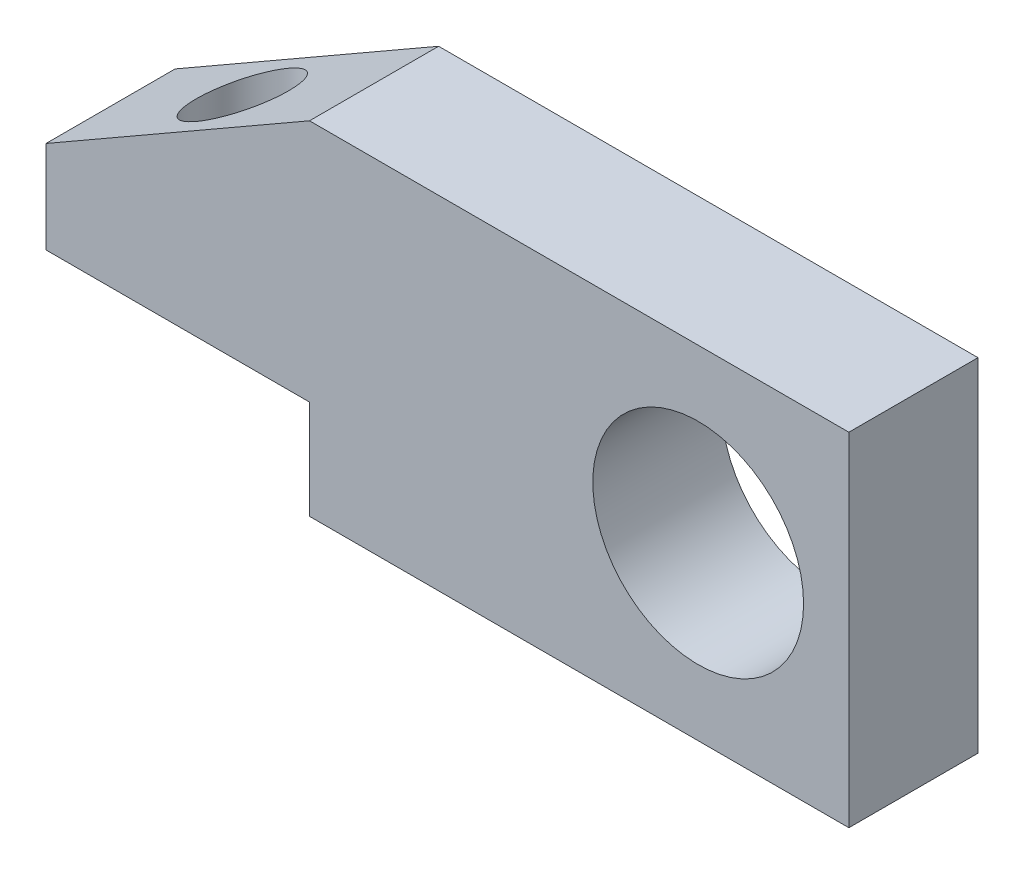
SolidWorks part; units mm, degrees
material "ABS"
ref_plane "Front Plane" through (0, 0, 0) normal (0, 0, 1) x (1, 0, 0)
ref_plane "Top Plane" through (0, 0, 0) normal (0, 1, 0) x (1, 0, 0)
ref_plane "Right Plane" through (0, 0, 0) normal (1, 0, 0) x (0, 0, -1)
sketch "Sketch1" plane through (0, 0, 0) normal (0, 0, 1) x (1, 0, 0)
  line L0 (-24, 15) -> (0, 15)
  line L1 (0, 15) -> (0, 0)
  line L2 (0, 0) -> (93, 0)
  line L3 (93, 0) -> (93, 102.7)
  line L4 (93, 102.7) -> (0, 102.7)
  line L5 (0, 102.7) -> (0, 30)
  line L6 (0, 30) -> (-24, 30)
  line L7 (-24, 30) -> (-24, 15)
  circle A0 centre (15, 10.5) radius 8
  circle A1 centre (70, 72) radius 11
  circle A2 centre (15, 10.5) radius 11
  dimension "D1" = 15
  dimension "D10" = 16
  dimension "D11" = 22
  dimension "D12" = 22
  dimension "D2" = 24
  dimension "D3" = 72.7
  dimension "D4" = 15
  dimension "D5" = 15
  dimension "D6" = 10.5
  dimension "D7" = 82.5061
  dimension "D8" = 72
  dimension "D9" = 93
extrude "Boss-Extrude1" add sketch "Sketch1" along normal blind 4.8 contours A2 L2 L3 L4 L5 L6 L7 L0 L1 A1 | L2 A2 A0 region at (44.5238, 51.0418, 0) region at (8.6656, 19.1141, 0)
sketch "Sketch2" plane through (0, 0, 4.8) normal (0, 0, 1) x (1, 0, 0)
  line L0 (93, 0) -> (93, 102.7) construction
  line L1 (48.1786, 92.7632) -> (93, 92.7632)
  line L2 (48.1786, 92.7632) -> (48.1786, 52.666)
  line L3 (48.1786, 52.666) -> (93, 52.666)
  line L4 (93, 92.7632) -> (93, 52.666)
  line L5 (48.1786, 92.7632) -> (93, 52.666) construction
  line L6 (48.1786, 52.666) -> (93, 92.7632) construction
  circle A0 centre (70, 72) radius 11
  circle A1 centre (70, 72) radius 4.15
  point P8 (70.5893, 72.7146)
  line M4 (93, 0) -> (93, 102.7)
  circle M10 centre (70, 72) radius 11
  dimension "D1" = 22
  dimension "D2" = 8.3
extrude "Boss-Extrude2" add sketch "Sketch2" along normal blind 8.2 contours L2 L3 L1 M4 M10 region at (70.5893, 92.1618, 4.8)
sketch "Sketch3" plane through (0, 0, 4.8) normal (0, 0, 1) x (1, 0, 0)
  line L1 (-24, 15) -> (0, 15)
  line L2 (-24, 15) -> (-24, 30)
  line L3 (-24, 30) -> (0, 30)
  line L4 (0, 15) -> (0, 30)
  line L5 (-24, 15) -> (0, 30) construction
  line L6 (-24, 30) -> (0, 15) construction
  line L7 (0, 0) -> (93, 0)
  line L8 (0, 0) -> (0, 52.666)
  line L9 (0, 52.666) -> (93, 52.666)
  line L10 (93, 0) -> (93, 52.666)
  circle A0 centre (15, 10.5) radius 8
  point P4 (-12, 22.5)
  point P11 (46.5, 26.333)
  circle M1 centre (15, 10.5) radius 8
  line M6 (0, 102.7) -> (0, 30)
  line M7 (0, 30) -> (-24, 30)
  line M8 (-24, 30) -> (-24, 15)
  line M9 (-24, 15) -> (0, 15)
  line M10 (0, 15) -> (0, 0)
  line M11 (0, 0) -> (93, 0)
  line M12 (93, 0) -> (93, 52.666)
  line M13 (93, 52.666) -> (48.1786, 52.666)
  dimension "D1" = 93
extrude "Boss-Extrude3" add sketch "Sketch3" along normal blind 5 contours L4 M9 M7 M8 | L9 L4 M6 M10 M11 M12 M13 M1 region at (-12, 22.5, 4.8) region at (47.8484, 27.0108, 4.8)
sketch "Sketch4" plane through (0, 83.2317, 0) normal (0, -1, 0) x (1, 0, 0)
  line L0 (0, 9.8) -> (0, 4.8) construction
  line L1 (0, 4.8) -> (48.1786, 4.8)
  line L2 (0, 4.8) -> (0, 45.3)
  line L3 (0, 45.3) -> (48.1786, 45.3)
  line L4 (48.1786, 4.8) -> (48.1786, 45.3)
  line L5 (0, 4.8) -> (48.1786, 45.3) construction
  line L6 (0, 45.3) -> (48.1786, 4.8) construction
  line L7 (0, 4.8) -> (48.1786, 4.8) construction
  line L8 (48.1786, 13) -> (48.1786, 9.8) construction
  line L9 (0, 0) -> (93, 0) construction
  line L10 (0, 45.3) -> (-5, 45.3)
  line L11 (0, 45.3) -> (0, 0)
  line L12 (0, 0) -> (-5, 0)
  line L13 (-5, 45.3) -> (-5, 0)
  line L14 (0, 45.3) -> (-5, 0) construction
  line L15 (0, 0) -> (-5, 45.3) construction
  circle A0 centre (13.9465, 30.3) radius 6.35
  circle A1 centre (13.9465, 23.3) radius 18.5
  circle A3 centre (29.4465, 23.3) radius 2
  circle A4 centre (21.6965, 9.8766) radius 2
  circle A5 centre (6.1965, 9.8766) radius 2
  point P10 (24.0893, 25.05)
  point P30 (-2.5, 22.65)
  arc M5 (5.039, 30.9329) -> (22.854, 30.9329) centre (13.9465, 30.3) ccw
  arc M7 (23.1854, 31.0672) -> (4.7077, 31.0672) centre (13.9465, 23.3) cw
  circle M9 centre (21.6965, 9.8766) radius 1.6
  circle M10 centre (6.1965, 9.8766) radius 1.6
  circle M11 centre (-1.5535, 23.3) radius 1.6
  circle M12 centre (6.1965, 36.7234) radius 1.6
  circle M13 centre (21.6965, 36.7234) radius 1.6
  circle M15 centre (27.3699, 31.05) radius 2.1
  circle M16 centre (0.5231, 31.05) radius 2.1
  circle M17 centre (13.9465, 7.8) radius 2.1
  circle M19 centre (13.9465, 23.3) radius 18.5
  dimension "D1" = 12.7
  dimension "D2" = 15
  dimension "D3" = 4
  dimension "D4" = 4
  dimension "D5" = 4
  dimension "D6" = 5
  dimension "D7" = 0
extrude "Boss-Extrude4" add sketch "Sketch4" along normal blind 5 contours L1 L4 L3 M19 | A0 L3 L2 A5 A4 A3 M12 M19 M16 M11 M13 M17 M15 M5 M7 | M5 M7 | M17 | A4 M9 | M9 | M10 | A5 M10 | M15 | L2 M16 | L2 L1 M19 region at (3.3557, 83.2317, 6.6306) region at (34.3643, 83.2317, 27.4815) region at (15.1399, 83.2317, 22.3686) region at (1.1393, 83.2317, 31.05) region at (19.7531, 83.2317, 9.8766) region at (4.2531, 83.2317, 9.8766) region at (21.6965, 83.2317, 9.8766) region at (6.1965, 83.2317, 9.8766) region at (27.3699, 83.2317, 31.05) region at (13.9465, 83.2317, 7.8)
sketch "Sketch5" plane through (48.1786, 0, 0) normal (1, 0, 0) x (0, 0, -1)
  line L0 (-45.3, 83.2317) -> (-13, 92.7632)
  line L1 (-13, 92.7632) -> (-4.8, 92.7632)
  line L2 (-4.8, 92.7632) -> (-4.8, 78.2317)
  line L3 (-4.8, 78.2317) -> (-45.3, 78.2317)
  line L4 (-45.3, 78.2317) -> (-45.3, 83.2317)
extrude "Boss-Extrude5" add sketch "Sketch5" against normal blind 5
sketch "Sketch6" plane through (0, 0, 4.8) normal (0, 0, 1) x (1, 0, 0)
  line L0 (0, 78.2317) -> (0, 52.666) construction
  line L1 (0, 78.2317) -> (48.1786, 78.2317)
  line L2 (0, 78.2317) -> (0, 52.666)
  line L3 (0, 52.666) -> (48.1786, 52.666)
  line L4 (48.1786, 78.2317) -> (48.1786, 52.666)
  line L5 (0, 78.2317) -> (48.1786, 52.666) construction
  line L6 (0, 52.666) -> (48.1786, 78.2317) construction
  line L7 (0, 78.2317) -> (48.1786, 78.2317) construction
  point P4 (24.0893, 65.4489)
extrude "Boss-Extrude6" add sketch "Sketch6" along normal up to surface (5 mm away) up to face at (20.6865, 27.5553, 9.8)
ref_plane "Plane1" through (3.9877, 7.5909, 34.4544) normal (0.9262, 0.2454, -0.2862) x (0.0581, -0.8429, -0.5349)
sketch "Sketch8" plane through (0, 30, 0) normal (0, 1, 0) x (1, 0, 0)
  line L0 (0, 0) -> (-24, -9.8)
  line L1 (-24, -9.8) -> (-24, 0)
  line L2 (-24, 0) -> (0, -9.8)
  circle A0 centre (-12, -4.9) radius 2
  dimension "D1" = 4
extrude "Cut-Extrude1" cut sketch "Sketch8" against normal through all contours A0
sketch "Sketch9" plane through (0, 0, 0) normal (0, 0, -1) x (-1, 0, 0)
  line L1 (0, 30) -> (-93, 30)
  line L2 (0, 30) -> (0, 102.7)
  line L3 (0, 102.7) -> (-93, 102.7)
  line L4 (-93, 30) -> (-93, 102.7)
extrude "Cut-Extrude2" cut sketch "Sketch9" against normal blind 100
sketch "Sketch10" plane through (0, 0, 9.8) normal (0, 0, 1) x (1, 0, 0)
  line L0 (93, 30) -> (-24, 30) construction
  line L1 (93, 0) -> (26.438, 0)
  line L2 (93, 0) -> (93, 30)
  line L3 (93, 30) -> (26.438, 30)
  line L4 (26.438, 0) -> (26.438, 30)
extrude "Cut-Extrude3" cut sketch "Sketch10" against normal blind 100
sketch "Sketch11" plane through (0, 0, 0) normal (0, 0, -1) x (-1, 0, 0)
  line L0 (24, 30) -> (24, 15) construction
  line L1 (0, 15) -> (24, 15)
  line L2 (0, 15) -> (0, 30)
  line L3 (0, 30) -> (24, 30)
  line L4 (24, 15) -> (24, 30)
  line L5 (-26.438, 30) -> (24, 30) construction
extrude "Boss-Extrude7" add sketch "Sketch11" along normal blind 12
sketch "Sketch13" plane through (-24, 0, 0) normal (-1, 0, 0) x (0, 0, 1)
  line L0 (9.8, 30) -> (9.8, 15) construction
  line L1 (-12, 30) -> (9.8, 30)
  line L2 (-12, 30) -> (-12, 25)
  line L3 (-12, 25) -> (9.8, 25)
  line L4 (9.8, 30) -> (9.8, 25)
  dimension "D1" = 5
extrude "Cut-Extrude4" cut sketch "Sketch13" against normal blind 200
sketch "Sketch15" plane through (0, 25, 0) normal (0, 1, 0) x (1, 0, 0)
  circle A0 centre (-12, 5.1) radius 2
  circle A1 centre (-12, -4.9) radius 2 construction
  dimension "D1" = 4
  dimension "D2" = 10
  dimension "D3" = 0
extrude "Cut-Extrude5" cut sketch "Sketch15" against normal blind 200
sketch "Sketch16" plane through (0, 25, 0) normal (0, 1, 0) x (1, 0, 0)
  line L1 (0, 0) -> (-24, 0)
  line L2 (0, 0) -> (0, 12)
  line L3 (0, 12) -> (-24, 12)
  line L4 (-24, 0) -> (-24, 12)
extrude "Cut-Extrude6" cut sketch "Sketch16" against normal blind 10
sketch "Sketch17" plane through (0, 0, 0) normal (0, 0, -1) x (-1, 0, 0)
  line L0 (24, 15) -> (24, 25) construction
  line L1 (0, 15) -> (24, 15)
  line L2 (0, 15) -> (0, 19.51)
  line L3 (0, 19.51) -> (24, 19.51)
  line L4 (24, 15) -> (24, 19.51)
  line L5 (0, 15) -> (24, 19.51) construction
  line L6 (0, 19.51) -> (24, 15) construction
  point P4 (12, 17.255)
  point P8 (0, 0)
extrude "Cut-Extrude7" cut sketch "Sketch17" against normal through all
sketch "Sketch18" plane through (0, 25, 0) normal (0, 1, 0) x (1, 0, 0)
  line L1 (26.438, 0) -> (-0.002, 0)
  line L2 (26.438, 0) -> (26.438, -9.8)
  line L3 (26.438, -9.8) -> (-0.002, -9.8)
  line L4 (-0.002, 0) -> (-0.002, -9.8)
  dimension "D1" = 26.44
extrude "Boss-Extrude8" add sketch "Sketch18" along normal blind 14.5
sketch "Sketch19" plane through (0, 0, 0) normal (-1, 0, 0) x (0, 0, 1)
  line L0 (0, 19.51) -> (0, 0) construction
  line L1 (0, 5.01) -> (9.8, 5.01)
  line L2 (0, 5.01) -> (0, 12.01)
  line L3 (0, 12.01) -> (9.8, 12.01)
  line L4 (9.8, 5.01) -> (9.8, 12.01)
  line L5 (9.8, 19.51) -> (9.8, 0) construction
  line L8 (9.8, 19.51) -> (0, 19.51) construction
  dimension "D1" = 14.5
  dimension "D2" = 7
extrude "Boss-Extrude9" add sketch "Sketch19" along normal blind 34.5
sketch "Sketch20" plane through (0, 5.01, 0) normal (0, -1, 0) x (1, 0, 0)
  line L0 (-34.5, 9.8) -> (0, 9.8) construction
  line L1 (-34.5, 0) -> (-34.5, 9.8) construction
  circle A1 centre (-24.5, 4.9) radius 2
  dimension "D1" = 4
  dimension "D2" = 4.9
  dimension "D3" = 10
extrude "Cut-Extrude8" cut sketch "Sketch20" against normal blind 20
sketch "Sketch21" plane through (0, 0, 0) normal (0, 0, -1) x (-1, 0, 0)
  line L1 (24, 25) -> (0, 25)
  line L2 (24, 25) -> (24, 19.51)
  line L3 (24, 19.51) -> (0, 19.51)
  line L4 (0, 25) -> (0, 19.51)
extrude "Cut-Extrude9" cut sketch "Sketch21" against normal blind 20
sketch "Sketch22" plane through (0, 0, 0) normal (0, 0, -1) x (-1, 0, 0)
  line L0 (-26.438, 39.5) -> (-26.438, 0) construction
  line L1 (0.002, 39.5) -> (-26.438, 39.5)
  line L2 (0.002, 39.5) -> (0.002, 23.5)
  line L3 (0.002, 23.5) -> (-26.438, 23.5)
  line L4 (-26.438, 39.5) -> (-26.438, 23.5)
  circle A0 centre (-15, 10.5) radius 8 construction
  dimension "D1" = 13
extrude "Cut-Extrude10" cut sketch "Sketch22" against normal blind 20
sketch "Sketch23" plane through (0, 0, 0) normal (0, -1, 0) x (1, 0, 0)
  line L1 (0, 0) -> (26.438, 0)
  line L2 (0, 0) -> (0, 9.8)
  line L3 (0, 9.8) -> (26.438, 9.8)
  line L4 (26.438, 0) -> (26.438, 9.8)
extrude "Boss-Extrude10" add sketch "Sketch23" along normal blind 2.5
sketch "Sketch24" plane through (0, 0, 0) normal (-1, 0, 0) x (0, 0, 1)
  line L1 (0, -2.5) -> (9.8, -2.5)
  line L2 (0, -2.5) -> (0, 23.5)
  line L3 (0, 23.5) -> (9.8, 23.5)
  line L4 (9.8, -2.5) -> (9.8, 23.5)
extrude "Boss-Extrude11" add sketch "Sketch24" along normal blind 14.5
sketch "Sketch25" plane through (0, 0, 0) normal (0, 0, -1) x (-1, 0, 0)
  line L0 (14.5, 12.01) -> (14.5, 23.5)
  line L2 (14.5, 23.5) -> (14.5, 12.01) construction
  line L3 (14.5, 23.5) -> (34.5, 12.01)
  line L4 (34.5, 12.01) -> (14.5, 12.01)
  point P5 (24.5, 12.01)
extrude "Boss-Extrude12" add sketch "Sketch25" against normal up to vertex (9.8 mm away) up to point (-34.5, 12.01, 9.8)
sketch "Sketch26" plane through (0, 12.01, 0) normal (0, -1, 0) x (1, 0, 0)
  circle A0 centre (-24.5, 4.9) radius 3.5
  dimension "D1" = 7
extrude "Cut-Extrude11" cut sketch "Sketch26" against normal blind 14.5
